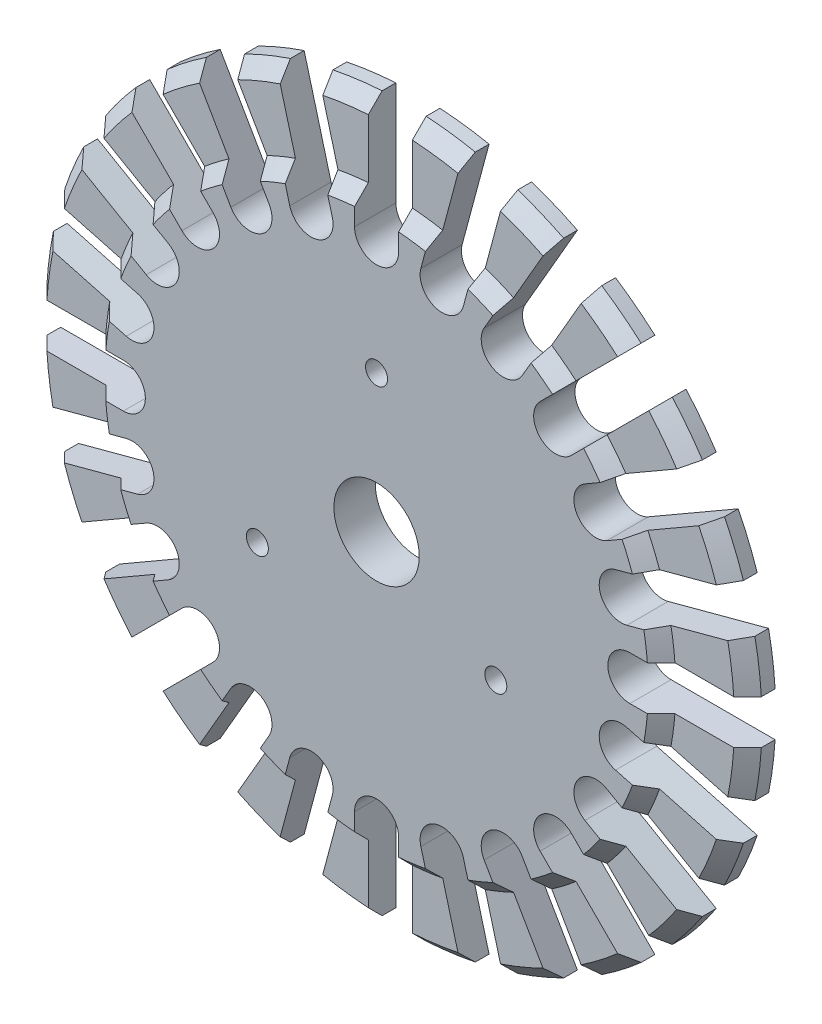
SolidWorks part; units mm, degrees
ref_plane "Plano frontal" through (0, 0, 0) normal (0, 0, 1) x (1, 0, 0)
ref_plane "Plano superior" through (0, 0, 0) normal (0, 1, 0) x (1, 0, 0)
ref_plane "Plano direito" through (0, 0, 0) normal (1, 0, 0) x (0, 0, -1)
sketch "Esboço1" plane through (0, 0, 0) normal (0, 0, 1) x (1, 0, 0)
  line L0 (0, 0) -> (26, 0) construction
  circle A0 centre (0, 0) radius 26
  dimension "R1" = 52
extrude "Ressalto-extrusão1" add sketch "Esboço1" along normal blind 2
fillet "Chanfro1" radius 1 1 edges at (26, 0, 2) type face fillet profile chamfer first side face at (26, 0, 2) second side face at (26, 0, 2)
sketch "Esboço3" plane through (0, 0, 0) normal (0, 0, -1) x (-1, 0, 0)
  line L0 (0, 0) -> (26, 0) construction
  line L1 (18.4, 1.6) -> (18.4, -1.6) construction
  line L2 (18.4, -1.6) -> (25.9507, -1.6)
  line L3 (18.4, 1.6) -> (25.9507, 1.6)
  line L4 (17.3589, -6.3078) -> (24.6524, -8.262)
  line L5 (18.1871, -3.2168) -> (25.4806, -5.1711)
  line L6 (0, 0) -> (25.1141, -6.7293) construction
  line L7 (15.1349, -10.5856) -> (21.674, -14.361)
  line L8 (16.7349, -7.8144) -> (23.274, -11.5897)
  line L9 (0, 0) -> (22.5167, -13) construction
  line L10 (11.8794, -14.1421) -> (17.2186, -19.4813)
  line L11 (14.1421, -11.8794) -> (19.4813, -17.2186)
  line L12 (0, 0) -> (18.3848, -18.3848) construction
  line L13 (7.8144, -16.7349) -> (11.5897, -23.274)
  line L14 (10.5856, -15.1349) -> (14.361, -21.674)
  line L15 (0, 0) -> (13, -22.5167) construction
  line L16 (3.2168, -18.1871) -> (5.1711, -25.4806)
  line L17 (6.3078, -17.3589) -> (8.262, -24.6524)
  line L18 (0, 0) -> (6.7293, -25.1141) construction
  line L19 (-1.6, -18.4) -> (-1.6, -25.9507)
  line L20 (1.6, -18.4) -> (1.6, -25.9507)
  line L21 (0, 0) -> (0, -26) construction
  line L22 (-6.3078, -17.3589) -> (-8.262, -24.6524)
  line L23 (-3.2168, -18.1871) -> (-5.1711, -25.4806)
  line L24 (0, 0) -> (-6.7293, -25.1141) construction
  line L25 (-10.5856, -15.1349) -> (-14.361, -21.674)
  line L26 (-7.8144, -16.7349) -> (-11.5897, -23.274)
  line L27 (0, 0) -> (-13, -22.5167) construction
  line L28 (-14.1421, -11.8794) -> (-19.4813, -17.2186)
  line L29 (-11.8794, -14.1421) -> (-17.2186, -19.4813)
  line L30 (0, 0) -> (-18.3848, -18.3848) construction
  line L31 (-16.7349, -7.8144) -> (-23.274, -11.5897)
  line L32 (-15.1349, -10.5856) -> (-21.674, -14.361)
  line L33 (0, 0) -> (-22.5167, -13) construction
  line L34 (-18.1871, -3.2168) -> (-25.4806, -5.1711)
  line L35 (-17.3589, -6.3078) -> (-24.6524, -8.262)
  line L36 (0, 0) -> (-25.1141, -6.7293) construction
  line L37 (-18.4, 1.6) -> (-25.9507, 1.6)
  line L38 (-18.4, -1.6) -> (-25.9507, -1.6)
  line L39 (0, 0) -> (-26, 0) construction
  line L40 (-17.3589, 6.3078) -> (-24.6524, 8.262)
  line L41 (-18.1871, 3.2168) -> (-25.4806, 5.1711)
  line L42 (0, 0) -> (-25.1141, 6.7293) construction
  line L43 (-15.1349, 10.5856) -> (-21.674, 14.361)
  line L44 (-16.7349, 7.8144) -> (-23.274, 11.5897)
  line L45 (0, 0) -> (-22.5167, 13) construction
  line L46 (-11.8794, 14.1421) -> (-17.2186, 19.4813)
  line L47 (-14.1421, 11.8794) -> (-19.4813, 17.2186)
  line L48 (0, 0) -> (-18.3848, 18.3848) construction
  line L49 (-7.8144, 16.7349) -> (-11.5897, 23.274)
  line L50 (-10.5856, 15.1349) -> (-14.361, 21.674)
  line L51 (0, 0) -> (-13, 22.5167) construction
  line L52 (-3.2168, 18.1871) -> (-5.1711, 25.4806)
  line L53 (-6.3078, 17.3589) -> (-8.262, 24.6524)
  line L54 (0, 0) -> (-6.7293, 25.1141) construction
  line L55 (1.6, 18.4) -> (1.6, 25.9507)
  line L56 (-1.6, 18.4) -> (-1.6, 25.9507)
  line L57 (0, 0) -> (0, 26) construction
  line L58 (6.3078, 17.3589) -> (8.262, 24.6524)
  line L59 (3.2168, 18.1871) -> (5.1711, 25.4806)
  line L60 (0, 0) -> (6.7293, 25.1141) construction
  line L61 (10.5856, 15.1349) -> (14.361, 21.674)
  line L62 (7.8144, 16.7349) -> (11.5897, 23.274)
  line L63 (0, 0) -> (13, 22.5167) construction
  line L64 (14.1421, 11.8794) -> (19.4813, 17.2186)
  line L65 (11.8794, 14.1421) -> (17.2186, 19.4813)
  line L66 (0, 0) -> (18.3848, 18.3848) construction
  line L67 (16.7349, 7.8144) -> (23.274, 11.5897)
  line L68 (15.1349, 10.5856) -> (21.674, 14.361)
  line L69 (0, 0) -> (22.5167, 13) construction
  line L70 (18.1871, 3.2168) -> (25.4806, 5.1711)
  line L71 (17.3589, 6.3078) -> (24.6524, 8.262)
  line L72 (0, 0) -> (25.1141, 6.7293) construction
  arc A1 (18.4, -1.6) -> (18.4, 1.6) centre (18.4, 0) cw
  arc A2 (25.9507, 1.6) -> (25.9507, -1.6) centre (0, 0) cw
  arc A3 (17.3589, -6.3078) -> (18.1871, -3.2168) centre (17.773, -4.7623) cw
  arc A4 (25.4806, -5.1711) -> (24.6524, -8.262) centre (0, 0) cw
  arc A5 (15.1349, -10.5856) -> (16.7349, -7.8144) centre (15.9349, -9.2) cw
  arc A6 (23.274, -11.5897) -> (21.674, -14.361) centre (0, 0) cw
  arc A7 (11.8794, -14.1421) -> (14.1421, -11.8794) centre (13.0108, -13.0108) cw
  arc A8 (19.4813, -17.2186) -> (17.2186, -19.4813) centre (0, 0) cw
  arc A9 (7.8144, -16.7349) -> (10.5856, -15.1349) centre (9.2, -15.9349) cw
  arc A10 (14.361, -21.674) -> (11.5897, -23.274) centre (0, 0) cw
  arc A11 (3.2168, -18.1871) -> (6.3078, -17.3589) centre (4.7623, -17.773) cw
  arc A12 (8.262, -24.6524) -> (5.1711, -25.4806) centre (0, 0) cw
  arc A13 (-1.6, -18.4) -> (1.6, -18.4) centre (0, -18.4) cw
  arc A14 (1.6, -25.9507) -> (-1.6, -25.9507) centre (0, 0) cw
  arc A15 (-6.3078, -17.3589) -> (-3.2168, -18.1871) centre (-4.7623, -17.773) cw
  arc A16 (-5.1711, -25.4806) -> (-8.262, -24.6524) centre (0, 0) cw
  arc A17 (-10.5856, -15.1349) -> (-7.8144, -16.7349) centre (-9.2, -15.9349) cw
  arc A18 (-11.5897, -23.274) -> (-14.361, -21.674) centre (0, 0) cw
  arc A19 (-14.1421, -11.8794) -> (-11.8794, -14.1421) centre (-13.0108, -13.0108) cw
  arc A20 (-17.2186, -19.4813) -> (-19.4813, -17.2186) centre (0, 0) cw
  arc A21 (-16.7349, -7.8144) -> (-15.1349, -10.5856) centre (-15.9349, -9.2) cw
  arc A22 (-21.674, -14.361) -> (-23.274, -11.5897) centre (0, 0) cw
  arc A23 (-18.1871, -3.2168) -> (-17.3589, -6.3078) centre (-17.773, -4.7623) cw
  arc A24 (-24.6524, -8.262) -> (-25.4806, -5.1711) centre (0, 0) cw
  arc A25 (-18.4, 1.6) -> (-18.4, -1.6) centre (-18.4, 0) cw
  arc A26 (-25.9507, -1.6) -> (-25.9507, 1.6) centre (0, 0) cw
  arc A27 (-17.3589, 6.3078) -> (-18.1871, 3.2168) centre (-17.773, 4.7623) cw
  arc A28 (-25.4806, 5.1711) -> (-24.6524, 8.262) centre (0, 0) cw
  arc A29 (-15.1349, 10.5856) -> (-16.7349, 7.8144) centre (-15.9349, 9.2) cw
  arc A30 (-23.274, 11.5897) -> (-21.674, 14.361) centre (0, 0) cw
  arc A31 (-11.8794, 14.1421) -> (-14.1421, 11.8794) centre (-13.0108, 13.0108) cw
  arc A32 (-19.4813, 17.2186) -> (-17.2186, 19.4813) centre (0, 0) cw
  arc A33 (-7.8144, 16.7349) -> (-10.5856, 15.1349) centre (-9.2, 15.9349) cw
  arc A34 (-14.361, 21.674) -> (-11.5897, 23.274) centre (0, 0) cw
  arc A35 (-3.2168, 18.1871) -> (-6.3078, 17.3589) centre (-4.7623, 17.773) cw
  arc A36 (-8.262, 24.6524) -> (-5.1711, 25.4806) centre (0, 0) cw
  arc A37 (1.6, 18.4) -> (-1.6, 18.4) centre (0, 18.4) cw
  arc A38 (-1.6, 25.9507) -> (1.6, 25.9507) centre (0, 0) cw
  arc A39 (6.3078, 17.3589) -> (3.2168, 18.1871) centre (4.7623, 17.773) cw
  arc A40 (5.1711, 25.4806) -> (8.262, 24.6524) centre (0, 0) cw
  arc A41 (10.5856, 15.1349) -> (7.8144, 16.7349) centre (9.2, 15.9349) cw
  arc A42 (11.5897, 23.274) -> (14.361, 21.674) centre (0, 0) cw
  arc A43 (14.1421, 11.8794) -> (11.8794, 14.1421) centre (13.0108, 13.0108) cw
  arc A44 (17.2186, 19.4813) -> (19.4813, 17.2186) centre (0, 0) cw
  arc A45 (16.7349, 7.8144) -> (15.1349, 10.5856) centre (15.9349, 9.2) cw
  arc A46 (21.674, 14.361) -> (23.274, 11.5897) centre (0, 0) cw
  arc A47 (18.1871, 3.2168) -> (17.3589, 6.3078) centre (17.773, 4.7623) cw
  arc A48 (24.6524, 8.262) -> (25.4806, 5.1711) centre (0, 0) cw
  circle A51 centre (0, 0) radius 26
  circle A53 centre (0, 0) radius 26
  point P9 (18.4, 0)
  point P20 (17.773, -4.7623)
  point P27 (15.9349, -9.2)
  point P34 (13.0108, -13.0108)
  point P41 (9.2, -15.9349)
  point P48 (4.7623, -17.773)
  point P55 (0, -18.4)
  point P62 (-4.7623, -17.773)
  point P69 (-9.2, -15.9349)
  point P76 (-13.0108, -13.0108)
  point P83 (-15.9349, -9.2)
  point P90 (-17.773, -4.7623)
  point P97 (-18.4, 0)
  point P104 (-17.773, 4.7623)
  point P111 (-15.9349, 9.2)
  point P118 (-13.0108, 13.0108)
  point P125 (-9.2, 15.9349)
  point P132 (-4.7623, 17.773)
  point P139 (0, 18.4)
  point P146 (4.7623, 17.773)
  point P153 (9.2, 15.9349)
  point P160 (13.0108, 13.0108)
  point P167 (15.9349, 9.2)
  point P174 (17.773, 4.7623)
  point P177 (0, 0)
  circle M5 centre (0, 0) radius 26
  dimension "D1" = 3.2
  dimension "D2" = 7.6
  dimension "D4" = 0
  dimension "D3" = 24
extrude "Corte-extrusão1" cut sketch "Esboço3" against normal through all contours A1 L2 L3 M5 | A3 L4 L5 M5 | A5 L7 L8 M5 | A7 L10 L11 M5 | A9 L13 L14 M5 | A11 L16 L17 M5 | A13 L19 L20 M5 | A15 L22 L23 M5 | A17 L25 L26 M5 | A19 L28 L29 M5 | A21 L31 L32 M5 | A23 L34 L35 M5 | A25 L37 L38 M5 | A29 L43 L44 M5 | A27 L40 L41 M5 | A31 L46 L47 M5 | A33 L49 L50 M5 | A37 L55 L56 M5 | A39 L58 L59 M5 | A41 L61 L62 M5 | A43 L64 L65 M5 | A47 L70 L71 M5 | A45 L67 L68 M5 | L52 A36 L53 A35 region at (-21.5563, 0, 0) region at (-20.8218, -5.5792, 0) region at (-20.8218, 5.5792, 0) region at (-18.6683, -10.7781, 0) region at (-18.6683, 10.7781, 0) region at (-15.2426, -15.2426, 0) region at (-15.2426, 15.2426, 0) region at (-10.7781, -18.6683, 0) region at (-10.7781, 18.6683, 0) region at (-5.5792, -20.8218, 0) region at (-5.5792, 20.8218, 0) region at (0, -21.5563, 0) region at (0, 21.5563, 0) region at (5.5792, -20.8218, 0) region at (10.7781, -18.6683, 0) region at (10.7781, 18.6683, 0) region at (15.2426, -15.2426, 0) region at (15.2426, 15.2426, 0) region at (18.6683, -10.7781, 0) region at (18.6683, 10.7781, 0) region at (20.8218, -5.5792, 0) region at (20.8218, 5.5792, 0) region at (21.5563, 0, 0)
sketch "Esboço4" plane through (0, 0, 0) normal (0, 0, -1) x (-1, 0, 0)
  line L0 (22.9466, 1.6) -> (22.9466, 2.6)
  line L1 (0, 0) -> (20.78, -7.2244) construction
  line L2 (25.9507, 1.6) -> (18.4, 1.6) construction
  line L3 (0, 0) -> (21.6082, -4.1335) construction
  line L4 (18.4, -1.6) -> (25.9507, -1.6) construction
  line L5 (0, 0) -> (0, 6.1074) construction
  line L6 (0, 0) -> (23.9466, 1.6) construction
  line L7 (0, 0) -> (23.9466, -1.6) construction
  line L8 (0, 0) -> (18.2021, -12.3565) construction
  line L9 (0, 0) -> (19.8021, -9.5852) construction
  line L10 (0, 0) -> (14.3838, -16.6465) construction
  line L11 (0, 0) -> (16.6465, -14.3838) construction
  line L12 (0, 0) -> (9.5852, -19.8021) construction
  line L13 (0, 0) -> (12.3565, -18.2021) construction
  line L14 (0, 0) -> (4.1335, -21.6082) construction
  line L15 (0, 0) -> (7.2244, -20.78) construction
  line L16 (0, 0) -> (-1.6, -21.9417) construction
  line L17 (0, 0) -> (1.6, -21.9417) construction
  line L18 (0, 0) -> (-7.2244, -20.78) construction
  line L19 (0, 0) -> (-4.1335, -21.6082) construction
  line L20 (0, 0) -> (-12.3565, -18.2021) construction
  line L21 (0, 0) -> (-9.5852, -19.8021) construction
  line L22 (0, 0) -> (-16.6465, -14.3838) construction
  line L23 (0, 0) -> (-14.3838, -16.6465) construction
  line L24 (0, 0) -> (-19.8021, -9.5852) construction
  line L25 (0, 0) -> (-18.2021, -12.3565) construction
  line L26 (0, 0) -> (-21.6082, -4.1335) construction
  line L27 (0, 0) -> (-20.78, -7.2244) construction
  line L28 (0, 0) -> (-21.9417, 1.6) construction
  line L29 (0, 0) -> (-21.9417, -1.6) construction
  line L30 (0, 0) -> (-20.78, 7.2244) construction
  line L31 (0, 0) -> (-21.6082, 4.1335) construction
  line L32 (0, 0) -> (-18.2021, 12.3565) construction
  line L33 (0, 0) -> (-19.8021, 9.5852) construction
  line L34 (0, 0) -> (-14.3838, 16.6465) construction
  line L35 (0, 0) -> (-16.6465, 14.3838) construction
  line L36 (0, 0) -> (-9.5852, 19.8021) construction
  line L37 (0, 0) -> (-12.3565, 18.2021) construction
  line L38 (0, 0) -> (-4.1335, 21.6082) construction
  line L39 (0, 0) -> (-7.2244, 20.78) construction
  line L40 (0, 0) -> (1.6, 21.9417) construction
  line L41 (0, 0) -> (-1.6, 21.9417) construction
  line L42 (0, 0) -> (7.2244, 20.78) construction
  line L43 (0, 0) -> (4.1335, 21.6082) construction
  line L44 (0, 0) -> (12.3565, 18.2021) construction
  line L45 (0, 0) -> (9.5852, 19.8021) construction
  line L52 (22.9466, 2.6) -> (24.9466, 2.6)
  line L54 (0, 0) -> (0, 10) construction
  line L55 (24.9466, -2.6) -> (22.9466, -2.6)
  line L57 (23.9466, 1.6) -> (23.9466, -1.6) construction
  line L58 (22.9466, -1.6) -> (22.9466, -2.6)
  line L59 (22.9466, 2.6) -> (22.9466, -2.6) construction
  line L60 (24.9466, -2.6) -> (24.9466, 2.6) construction
  line L61 (24.9466, -2.6) -> (24.9466, -1.6)
  line L62 (24.9466, -1.6) -> (22.9466, -1.6)
  line L63 (24.9466, 1.6) -> (22.9466, 1.6)
  line L64 (24.9466, 1.6) -> (24.9466, 2.6)
  line L65 (22.5788, -4.3935) -> (22.8377, -3.4276)
  line L66 (22.8377, -3.4276) -> (24.7695, -3.9452)
  line L67 (23.4236, -8.9681) -> (21.4918, -8.4504)
  line L68 (21.7506, -7.4845) -> (21.4918, -8.4504)
  line L69 (23.4236, -8.9681) -> (23.6825, -8.0021)
  line L70 (23.6825, -8.0021) -> (21.7506, -7.4845)
  line L71 (24.5107, -4.9112) -> (22.5788, -4.3935)
  line L72 (24.5107, -4.9112) -> (24.7695, -3.9452)
  line L73 (0, 0) -> (23.5448, -4.6524) construction
  line L74 (0, 0) -> (22.7165, -7.7433) construction
  line L75 (22.8377, -3.4276) -> (21.4918, -8.4504) construction
  line L76 (23.4236, -8.9681) -> (24.7695, -3.9452) construction
  line L77 (20.6723, -10.0877) -> (21.1723, -9.2216)
  line L78 (21.1723, -9.2216) -> (22.9044, -10.2216)
  line L79 (20.3044, -14.725) -> (18.5723, -13.725)
  line L80 (19.0723, -12.8589) -> (18.5723, -13.725)
  line L81 (20.3044, -14.725) -> (20.8044, -13.8589)
  line L82 (20.8044, -13.8589) -> (19.0723, -12.8589)
  line L83 (22.4044, -11.0877) -> (20.6723, -10.0877)
  line L84 (22.4044, -11.0877) -> (22.9044, -10.2216)
  line L85 (0, 0) -> (21.5384, -10.5877) construction
  line L86 (0, 0) -> (19.9384, -13.3589) construction
  line L87 (21.1723, -9.2216) -> (18.5723, -13.725) construction
  line L88 (20.3044, -14.725) -> (22.9044, -10.2216) construction
  line L89 (17.3571, -15.0943) -> (18.0642, -14.3872)
  line L90 (18.0642, -14.3872) -> (19.4784, -15.8014)
  line L91 (15.8014, -19.4784) -> (14.3872, -18.0642)
  line L92 (15.0943, -17.3571) -> (14.3872, -18.0642)
  line L93 (15.8014, -19.4784) -> (16.5085, -18.7713)
  line L94 (16.5085, -18.7713) -> (15.0943, -17.3571)
  line L95 (18.7713, -16.5085) -> (17.3571, -15.0943)
  line L96 (18.7713, -16.5085) -> (19.4784, -15.8014)
  line L97 (0, 0) -> (18.0642, -15.8014) construction
  line L98 (0, 0) -> (15.8014, -18.0642) construction
  line L99 (18.0642, -14.3872) -> (14.3872, -18.0642) construction
  line L100 (15.8014, -19.4784) -> (19.4784, -15.8014) construction
  line L101 (12.8589, -19.0723) -> (13.725, -18.5723)
  line L102 (13.725, -18.5723) -> (14.725, -20.3044)
  line L103 (10.2216, -22.9044) -> (9.2216, -21.1723)
  line L104 (10.0877, -20.6723) -> (9.2216, -21.1723)
  line L105 (10.2216, -22.9044) -> (11.0877, -22.4044)
  line L106 (11.0877, -22.4044) -> (10.0877, -20.6723)
  line L107 (13.8589, -20.8044) -> (12.8589, -19.0723)
  line L108 (13.8589, -20.8044) -> (14.725, -20.3044)
  line L109 (0, 0) -> (13.3589, -19.9384) construction
  line L110 (0, 0) -> (10.5877, -21.5384) construction
  line L111 (13.725, -18.5723) -> (9.2216, -21.1723) construction
  line L112 (10.2216, -22.9044) -> (14.725, -20.3044) construction
  line L113 (7.4845, -21.7506) -> (8.4504, -21.4918)
  line L114 (8.4504, -21.4918) -> (8.9681, -23.4236)
  line L115 (3.9452, -24.7695) -> (3.4276, -22.8377)
  line L116 (4.3935, -22.5788) -> (3.4276, -22.8377)
  line L117 (3.9452, -24.7695) -> (4.9112, -24.5107)
  line L118 (4.9112, -24.5107) -> (4.3935, -22.5788)
  line L119 (8.0021, -23.6825) -> (7.4845, -21.7506)
  line L120 (8.0021, -23.6825) -> (8.9681, -23.4236)
  line L121 (0, 0) -> (7.7433, -22.7165) construction
  line L122 (0, 0) -> (4.6524, -23.5448) construction
  line L123 (8.4504, -21.4918) -> (3.4276, -22.8377) construction
  line L124 (3.9452, -24.7695) -> (8.9681, -23.4236) construction
  line L125 (1.6, -22.9466) -> (2.6, -22.9466)
  line L126 (2.6, -22.9466) -> (2.6, -24.9466)
  line L127 (-2.6, -24.9466) -> (-2.6, -22.9466)
  line L128 (-1.6, -22.9466) -> (-2.6, -22.9466)
  line L129 (-2.6, -24.9466) -> (-1.6, -24.9466)
  line L130 (-1.6, -24.9466) -> (-1.6, -22.9466)
  line L131 (1.6, -24.9466) -> (1.6, -22.9466)
  line L132 (1.6, -24.9466) -> (2.6, -24.9466)
  line L133 (0, 0) -> (1.6, -23.9466) construction
  line L134 (0, 0) -> (-1.6, -23.9466) construction
  line L135 (2.6, -22.9466) -> (-2.6, -22.9466) construction
  line L136 (-2.6, -24.9466) -> (2.6, -24.9466) construction
  line L137 (-4.3935, -22.5788) -> (-3.4276, -22.8377)
  line L138 (-3.4276, -22.8377) -> (-3.9452, -24.7695)
  line L139 (-8.9681, -23.4236) -> (-8.4504, -21.4918)
  line L140 (-7.4845, -21.7506) -> (-8.4504, -21.4918)
  line L141 (-8.9681, -23.4236) -> (-8.0021, -23.6825)
  line L142 (-8.0021, -23.6825) -> (-7.4845, -21.7506)
  line L143 (-4.9112, -24.5107) -> (-4.3935, -22.5788)
  line L144 (-4.9112, -24.5107) -> (-3.9452, -24.7695)
  line L145 (0, 0) -> (-4.6524, -23.5448) construction
  line L146 (0, 0) -> (-7.7433, -22.7165) construction
  line L147 (-3.4276, -22.8377) -> (-8.4504, -21.4918) construction
  line L148 (-8.9681, -23.4236) -> (-3.9452, -24.7695) construction
  line L149 (-10.0877, -20.6723) -> (-9.2216, -21.1723)
  line L150 (-9.2216, -21.1723) -> (-10.2216, -22.9044)
  line L151 (-14.725, -20.3044) -> (-13.725, -18.5723)
  line L152 (-12.8589, -19.0723) -> (-13.725, -18.5723)
  line L153 (-14.725, -20.3044) -> (-13.8589, -20.8044)
  line L154 (-13.8589, -20.8044) -> (-12.8589, -19.0723)
  line L155 (-11.0877, -22.4044) -> (-10.0877, -20.6723)
  line L156 (-11.0877, -22.4044) -> (-10.2216, -22.9044)
  line L157 (0, 0) -> (-10.5877, -21.5384) construction
  line L158 (0, 0) -> (-13.3589, -19.9384) construction
  line L159 (-9.2216, -21.1723) -> (-13.725, -18.5723) construction
  line L160 (-14.725, -20.3044) -> (-10.2216, -22.9044) construction
  line L161 (-15.0943, -17.3571) -> (-14.3872, -18.0642)
  line L162 (-14.3872, -18.0642) -> (-15.8014, -19.4784)
  line L163 (-19.4784, -15.8014) -> (-18.0642, -14.3872)
  line L164 (-17.3571, -15.0943) -> (-18.0642, -14.3872)
  line L165 (-19.4784, -15.8014) -> (-18.7713, -16.5085)
  line L166 (-18.7713, -16.5085) -> (-17.3571, -15.0943)
  line L167 (-16.5085, -18.7713) -> (-15.0943, -17.3571)
  line L168 (-16.5085, -18.7713) -> (-15.8014, -19.4784)
  line L169 (0, 0) -> (-15.8014, -18.0642) construction
  line L170 (0, 0) -> (-18.0642, -15.8014) construction
  line L171 (-14.3872, -18.0642) -> (-18.0642, -14.3872) construction
  line L172 (-19.4784, -15.8014) -> (-15.8014, -19.4784) construction
  line L173 (-19.0723, -12.8589) -> (-18.5723, -13.725)
  line L174 (-18.5723, -13.725) -> (-20.3044, -14.725)
  line L175 (-22.9044, -10.2216) -> (-21.1723, -9.2216)
  line L176 (-20.6723, -10.0877) -> (-21.1723, -9.2216)
  line L177 (-22.9044, -10.2216) -> (-22.4044, -11.0877)
  line L178 (-22.4044, -11.0877) -> (-20.6723, -10.0877)
  line L179 (-20.8044, -13.8589) -> (-19.0723, -12.8589)
  line L180 (-20.8044, -13.8589) -> (-20.3044, -14.725)
  line L181 (0, 0) -> (-19.9384, -13.3589) construction
  line L182 (0, 0) -> (-21.5384, -10.5877) construction
  line L183 (-18.5723, -13.725) -> (-21.1723, -9.2216) construction
  line L184 (-22.9044, -10.2216) -> (-20.3044, -14.725) construction
  line L185 (-21.7506, -7.4845) -> (-21.4918, -8.4504)
  line L186 (-21.4918, -8.4504) -> (-23.4236, -8.9681)
  line L187 (-24.7695, -3.9452) -> (-22.8377, -3.4276)
  line L188 (-22.5788, -4.3935) -> (-22.8377, -3.4276)
  line L189 (-24.7695, -3.9452) -> (-24.5107, -4.9112)
  line L190 (-24.5107, -4.9112) -> (-22.5788, -4.3935)
  line L191 (-23.6825, -8.0021) -> (-21.7506, -7.4845)
  line L192 (-23.6825, -8.0021) -> (-23.4236, -8.9681)
  line L193 (0, 0) -> (-22.7165, -7.7433) construction
  line L194 (0, 0) -> (-23.5448, -4.6524) construction
  line L195 (-21.4918, -8.4504) -> (-22.8377, -3.4276) construction
  line L196 (-24.7695, -3.9452) -> (-23.4236, -8.9681) construction
  line L197 (-22.9466, -1.6) -> (-22.9466, -2.6)
  line L198 (-22.9466, -2.6) -> (-24.9466, -2.6)
  line L199 (-24.9466, 2.6) -> (-22.9466, 2.6)
  line L200 (-22.9466, 1.6) -> (-22.9466, 2.6)
  line L201 (-24.9466, 2.6) -> (-24.9466, 1.6)
  line L202 (-24.9466, 1.6) -> (-22.9466, 1.6)
  line L203 (-24.9466, -1.6) -> (-22.9466, -1.6)
  line L204 (-24.9466, -1.6) -> (-24.9466, -2.6)
  line L205 (0, 0) -> (-23.9466, -1.6) construction
  line L206 (0, 0) -> (-23.9466, 1.6) construction
  line L207 (-22.9466, -2.6) -> (-22.9466, 2.6) construction
  line L208 (-24.9466, 2.6) -> (-24.9466, -2.6) construction
  line L209 (-22.5788, 4.3935) -> (-22.8377, 3.4276)
  line L210 (-22.8377, 3.4276) -> (-24.7695, 3.9452)
  line L211 (-23.4236, 8.9681) -> (-21.4918, 8.4504)
  line L212 (-21.7506, 7.4845) -> (-21.4918, 8.4504)
  line L213 (-23.4236, 8.9681) -> (-23.6825, 8.0021)
  line L214 (-23.6825, 8.0021) -> (-21.7506, 7.4845)
  line L215 (-24.5107, 4.9112) -> (-22.5788, 4.3935)
  line L216 (-24.5107, 4.9112) -> (-24.7695, 3.9452)
  line L217 (0, 0) -> (-23.5448, 4.6524) construction
  line L218 (0, 0) -> (-22.7165, 7.7433) construction
  line L219 (-22.8377, 3.4276) -> (-21.4918, 8.4504) construction
  line L220 (-23.4236, 8.9681) -> (-24.7695, 3.9452) construction
  line L221 (-20.6723, 10.0877) -> (-21.1723, 9.2216)
  line L222 (-21.1723, 9.2216) -> (-22.9044, 10.2216)
  line L223 (-20.3044, 14.725) -> (-18.5723, 13.725)
  line L224 (-19.0723, 12.8589) -> (-18.5723, 13.725)
  line L225 (-20.3044, 14.725) -> (-20.8044, 13.8589)
  line L226 (-20.8044, 13.8589) -> (-19.0723, 12.8589)
  line L227 (-22.4044, 11.0877) -> (-20.6723, 10.0877)
  line L228 (-22.4044, 11.0877) -> (-22.9044, 10.2216)
  line L229 (0, 0) -> (-21.5384, 10.5877) construction
  line L230 (0, 0) -> (-19.9384, 13.3589) construction
  line L231 (-21.1723, 9.2216) -> (-18.5723, 13.725) construction
  line L232 (-20.3044, 14.725) -> (-22.9044, 10.2216) construction
  line L233 (-17.3571, 15.0943) -> (-18.0642, 14.3872)
  line L234 (-18.0642, 14.3872) -> (-19.4784, 15.8014)
  line L235 (-15.8014, 19.4784) -> (-14.3872, 18.0642)
  line L236 (-15.0943, 17.3571) -> (-14.3872, 18.0642)
  line L237 (-15.8014, 19.4784) -> (-16.5085, 18.7713)
  line L238 (-16.5085, 18.7713) -> (-15.0943, 17.3571)
  line L239 (-18.7713, 16.5085) -> (-17.3571, 15.0943)
  line L240 (-18.7713, 16.5085) -> (-19.4784, 15.8014)
  line L241 (0, 0) -> (-18.0642, 15.8014) construction
  line L242 (0, 0) -> (-15.8014, 18.0642) construction
  line L243 (-18.0642, 14.3872) -> (-14.3872, 18.0642) construction
  line L244 (-15.8014, 19.4784) -> (-19.4784, 15.8014) construction
  line L245 (-12.8589, 19.0723) -> (-13.725, 18.5723)
  line L246 (-13.725, 18.5723) -> (-14.725, 20.3044)
  line L247 (-10.2216, 22.9044) -> (-9.2216, 21.1723)
  line L248 (-10.0877, 20.6723) -> (-9.2216, 21.1723)
  line L249 (-10.2216, 22.9044) -> (-11.0877, 22.4044)
  line L250 (-11.0877, 22.4044) -> (-10.0877, 20.6723)
  line L251 (-13.8589, 20.8044) -> (-12.8589, 19.0723)
  line L252 (-13.8589, 20.8044) -> (-14.725, 20.3044)
  line L253 (0, 0) -> (-13.3589, 19.9384) construction
  line L254 (0, 0) -> (-10.5877, 21.5384) construction
  line L255 (-13.725, 18.5723) -> (-9.2216, 21.1723) construction
  line L256 (-10.2216, 22.9044) -> (-14.725, 20.3044) construction
  line L257 (-7.4845, 21.7506) -> (-8.4504, 21.4918)
  line L258 (-8.4504, 21.4918) -> (-8.9681, 23.4236)
  line L259 (-3.9452, 24.7695) -> (-3.4276, 22.8377)
  line L260 (-4.3935, 22.5788) -> (-3.4276, 22.8377)
  line L261 (-3.9452, 24.7695) -> (-4.9112, 24.5107)
  line L262 (-4.9112, 24.5107) -> (-4.3935, 22.5788)
  line L263 (-8.0021, 23.6825) -> (-7.4845, 21.7506)
  line L264 (-8.0021, 23.6825) -> (-8.9681, 23.4236)
  line L265 (0, 0) -> (-7.7433, 22.7165) construction
  line L266 (0, 0) -> (-4.6524, 23.5448) construction
  line L267 (-8.4504, 21.4918) -> (-3.4276, 22.8377) construction
  line L268 (-3.9452, 24.7695) -> (-8.9681, 23.4236) construction
  line L269 (-1.6, 22.9466) -> (-2.6, 22.9466)
  line L270 (-2.6, 22.9466) -> (-2.6, 24.9466)
  line L271 (2.6, 24.9466) -> (2.6, 22.9466)
  line L272 (1.6, 22.9466) -> (2.6, 22.9466)
  line L273 (2.6, 24.9466) -> (1.6, 24.9466)
  line L274 (1.6, 24.9466) -> (1.6, 22.9466)
  line L275 (-1.6, 24.9466) -> (-1.6, 22.9466)
  line L276 (-1.6, 24.9466) -> (-2.6, 24.9466)
  line L277 (0, 0) -> (-1.6, 23.9466) construction
  line L278 (0, 0) -> (1.6, 23.9466) construction
  line L279 (-2.6, 22.9466) -> (2.6, 22.9466) construction
  line L280 (2.6, 24.9466) -> (-2.6, 24.9466) construction
  line L281 (4.3935, 22.5788) -> (3.4276, 22.8377)
  line L282 (3.4276, 22.8377) -> (3.9452, 24.7695)
  line L283 (8.9681, 23.4236) -> (8.4504, 21.4918)
  line L284 (7.4845, 21.7506) -> (8.4504, 21.4918)
  line L285 (8.9681, 23.4236) -> (8.0021, 23.6825)
  line L286 (8.0021, 23.6825) -> (7.4845, 21.7506)
  line L287 (4.9112, 24.5107) -> (4.3935, 22.5788)
  line L288 (4.9112, 24.5107) -> (3.9452, 24.7695)
  line L289 (0, 0) -> (4.6524, 23.5448) construction
  line L290 (0, 0) -> (7.7433, 22.7165) construction
  line L291 (3.4276, 22.8377) -> (8.4504, 21.4918) construction
  line L292 (8.9681, 23.4236) -> (3.9452, 24.7695) construction
  line L293 (10.0877, 20.6723) -> (9.2216, 21.1723)
  line L294 (9.2216, 21.1723) -> (10.2216, 22.9044)
  line L295 (14.725, 20.3044) -> (13.725, 18.5723)
  line L296 (12.8589, 19.0723) -> (13.725, 18.5723)
  line L297 (14.725, 20.3044) -> (13.8589, 20.8044)
  line L298 (13.8589, 20.8044) -> (12.8589, 19.0723)
  line L299 (11.0877, 22.4044) -> (10.0877, 20.6723)
  line L300 (11.0877, 22.4044) -> (10.2216, 22.9044)
  line L301 (0, 0) -> (10.5877, 21.5384) construction
  line L302 (0, 0) -> (13.3589, 19.9384) construction
  line L303 (9.2216, 21.1723) -> (13.725, 18.5723) construction
  line L304 (14.725, 20.3044) -> (10.2216, 22.9044) construction
  line L305 (15.0943, 17.3571) -> (14.3872, 18.0642)
  line L306 (14.3872, 18.0642) -> (15.8014, 19.4784)
  line L307 (19.4784, 15.8014) -> (18.0642, 14.3872)
  line L308 (17.3571, 15.0943) -> (18.0642, 14.3872)
  line L309 (19.4784, 15.8014) -> (18.7713, 16.5085)
  line L310 (18.7713, 16.5085) -> (17.3571, 15.0943)
  line L311 (16.5085, 18.7713) -> (15.0943, 17.3571)
  line L312 (16.5085, 18.7713) -> (15.8014, 19.4784)
  line L313 (0, 0) -> (15.8014, 18.0642) construction
  line L314 (0, 0) -> (18.0642, 15.8014) construction
  line L315 (14.3872, 18.0642) -> (18.0642, 14.3872) construction
  line L316 (19.4784, 15.8014) -> (15.8014, 19.4784) construction
  line L317 (19.0723, 12.8589) -> (18.5723, 13.725)
  line L318 (18.5723, 13.725) -> (20.3044, 14.725)
  line L319 (22.9044, 10.2216) -> (21.1723, 9.2216)
  line L320 (20.6723, 10.0877) -> (21.1723, 9.2216)
  line L321 (22.9044, 10.2216) -> (22.4044, 11.0877)
  line L322 (22.4044, 11.0877) -> (20.6723, 10.0877)
  line L323 (20.8044, 13.8589) -> (19.0723, 12.8589)
  line L324 (20.8044, 13.8589) -> (20.3044, 14.725)
  line L325 (0, 0) -> (19.9384, 13.3589) construction
  line L326 (0, 0) -> (21.5384, 10.5877) construction
  line L327 (18.5723, 13.725) -> (21.1723, 9.2216) construction
  line L328 (22.9044, 10.2216) -> (20.3044, 14.725) construction
  line L329 (21.7506, 7.4845) -> (21.4918, 8.4504)
  line L330 (21.4918, 8.4504) -> (23.4236, 8.9681)
  line L331 (24.7695, 3.9452) -> (22.8377, 3.4276)
  line L332 (22.5788, 4.3935) -> (22.8377, 3.4276)
  line L333 (24.7695, 3.9452) -> (24.5107, 4.9112)
  line L334 (24.5107, 4.9112) -> (22.5788, 4.3935)
  line L335 (23.6825, 8.0021) -> (21.7506, 7.4845)
  line L336 (23.6825, 8.0021) -> (23.4236, 8.9681)
  line L337 (0, 0) -> (22.7165, 7.7433) construction
  line L338 (0, 0) -> (23.5448, 4.6524) construction
  line L339 (21.4918, 8.4504) -> (22.8377, 3.4276) construction
  line L340 (24.7695, 3.9452) -> (23.4236, 8.9681) construction
  line L341 (0, 0) -> (8.6603, -5) construction
  line L342 (0, 0) -> (-8.6603, -5) construction
  point P5 (20.78, -7.2244)
  point P8 (23.9466, 1.6)
  point P11 (23.9466, -1.6)
  point P13 (22.9466, -1.6)
  point P20 (18.2021, -12.3565)
  point P23 (14.3838, -16.6465)
  point P26 (9.5852, -19.8021)
  point P29 (4.1335, -21.6082)
  point P32 (-1.6, -21.9417)
  point P35 (-7.2244, -20.78)
  point P38 (-12.3565, -18.2021)
  point P41 (-16.6465, -14.3838)
  point P44 (-19.8021, -9.5852)
  point P47 (-21.6082, -4.1335)
  point P50 (-21.9417, 1.6)
  point P53 (-20.78, 7.2244)
  point P56 (-18.2021, 12.3565)
  point P59 (-14.3838, 16.6465)
  point P62 (-9.5852, 19.8021)
  point P65 (-4.1335, 21.6082)
  point P68 (1.6, 21.9417)
  point P71 (7.2244, 20.78)
  point P74 (12.3565, 18.2021)
  point P86 (0, 0)
  point P90 (0, 0)
  point P93 (24.9466, -1.6)
  point P94 (24.9466, 1.6)
  point P95 (24.9466, 1.6)
  point P98 (23.9466, 2.6)
  point P108 (23.5448, -4.6524)
  point P109 (22.7165, -7.7433)
  point P110 (21.7506, -7.4845)
  point P115 (23.6825, -8.0021)
  point P116 (24.5107, -4.9112)
  point P117 (24.5107, -4.9112)
  point P124 (21.5384, -10.5877)
  point P125 (19.9384, -13.3589)
  point P126 (19.0723, -12.8589)
  point P131 (20.8044, -13.8589)
  point P132 (22.4044, -11.0877)
  point P133 (22.4044, -11.0877)
  point P140 (18.0642, -15.8014)
  point P141 (15.8014, -18.0642)
  point P142 (15.0943, -17.3571)
  point P147 (16.5085, -18.7713)
  point P148 (18.7713, -16.5085)
  point P149 (18.7713, -16.5085)
  point P156 (13.3589, -19.9384)
  point P157 (10.5877, -21.5384)
  point P158 (10.0877, -20.6723)
  point P163 (11.0877, -22.4044)
  point P164 (13.8589, -20.8044)
  point P165 (13.8589, -20.8044)
  point P172 (7.7433, -22.7165)
  point P173 (4.6524, -23.5448)
  point P174 (4.3935, -22.5788)
  point P179 (4.9112, -24.5107)
  point P180 (8.0021, -23.6825)
  point P181 (8.0021, -23.6825)
  point P188 (1.6, -23.9466)
  point P189 (-1.6, -23.9466)
  point P190 (-1.6, -22.9466)
  point P195 (-1.6, -24.9466)
  point P196 (1.6, -24.9466)
  point P197 (1.6, -24.9466)
  point P204 (-4.6524, -23.5448)
  point P205 (-7.7433, -22.7165)
  point P206 (-7.4845, -21.7506)
  point P211 (-8.0021, -23.6825)
  point P212 (-4.9112, -24.5107)
  point P213 (-4.9112, -24.5107)
  point P220 (-10.5877, -21.5384)
  point P221 (-13.3589, -19.9384)
  point P222 (-12.8589, -19.0723)
  point P227 (-13.8589, -20.8044)
  point P228 (-11.0877, -22.4044)
  point P229 (-11.0877, -22.4044)
  point P236 (-15.8014, -18.0642)
  point P237 (-18.0642, -15.8014)
  point P238 (-17.3571, -15.0943)
  point P243 (-18.7713, -16.5085)
  point P244 (-16.5085, -18.7713)
  point P245 (-16.5085, -18.7713)
  point P252 (-19.9384, -13.3589)
  point P253 (-21.5384, -10.5877)
  point P254 (-20.6723, -10.0877)
  point P259 (-22.4044, -11.0877)
  point P260 (-20.8044, -13.8589)
  point P261 (-20.8044, -13.8589)
  point P268 (-22.7165, -7.7433)
  point P269 (-23.5448, -4.6524)
  point P270 (-22.5788, -4.3935)
  point P275 (-24.5107, -4.9112)
  point P276 (-23.6825, -8.0021)
  point P277 (-23.6825, -8.0021)
  point P284 (-23.9466, -1.6)
  point P285 (-23.9466, 1.6)
  point P286 (-22.9466, 1.6)
  point P291 (-24.9466, 1.6)
  point P292 (-24.9466, -1.6)
  point P293 (-24.9466, -1.6)
  point P300 (-23.5448, 4.6524)
  point P301 (-22.7165, 7.7433)
  point P302 (-21.7506, 7.4845)
  point P307 (-23.6825, 8.0021)
  point P308 (-24.5107, 4.9112)
  point P309 (-24.5107, 4.9112)
  point P316 (-21.5384, 10.5877)
  point P317 (-19.9384, 13.3589)
  point P318 (-19.0723, 12.8589)
  point P323 (-20.8044, 13.8589)
  point P324 (-22.4044, 11.0877)
  point P325 (-22.4044, 11.0877)
  point P332 (-18.0642, 15.8014)
  point P333 (-15.8014, 18.0642)
  point P334 (-15.0943, 17.3571)
  point P339 (-16.5085, 18.7713)
  point P340 (-18.7713, 16.5085)
  point P341 (-18.7713, 16.5085)
  point P348 (-13.3589, 19.9384)
  point P349 (-10.5877, 21.5384)
  point P350 (-10.0877, 20.6723)
  point P355 (-11.0877, 22.4044)
  point P356 (-13.8589, 20.8044)
  point P357 (-13.8589, 20.8044)
  point P364 (-7.7433, 22.7165)
  point P365 (-4.6524, 23.5448)
  point P366 (-4.3935, 22.5788)
  point P371 (-4.9112, 24.5107)
  point P372 (-8.0021, 23.6825)
  point P373 (-8.0021, 23.6825)
  point P380 (-1.6, 23.9466)
  point P381 (1.6, 23.9466)
  point P382 (1.6, 22.9466)
  point P387 (1.6, 24.9466)
  point P388 (-1.6, 24.9466)
  point P389 (-1.6, 24.9466)
  point P396 (4.6524, 23.5448)
  point P397 (7.7433, 22.7165)
  point P398 (7.4845, 21.7506)
  point P403 (8.0021, 23.6825)
  point P404 (4.9112, 24.5107)
  point P405 (4.9112, 24.5107)
  point P412 (10.5877, 21.5384)
  point P413 (13.3589, 19.9384)
  point P414 (12.8589, 19.0723)
  point P419 (13.8589, 20.8044)
  point P420 (11.0877, 22.4044)
  point P421 (11.0877, 22.4044)
  point P428 (15.8014, 18.0642)
  point P429 (18.0642, 15.8014)
  point P430 (17.3571, 15.0943)
  point P435 (18.7713, 16.5085)
  point P436 (16.5085, 18.7713)
  point P437 (16.5085, 18.7713)
  point P444 (19.9384, 13.3589)
  point P445 (21.5384, 10.5877)
  point P446 (20.6723, 10.0877)
  point P451 (22.4044, 11.0877)
  point P452 (20.8044, 13.8589)
  point P453 (20.8044, 13.8589)
  point P460 (22.7165, 7.7433)
  point P461 (23.5448, 4.6524)
  point P462 (22.5788, 4.3935)
  point P467 (24.5107, 4.9112)
  point P468 (23.6825, 8.0021)
  point P469 (23.6825, 8.0021)
  point P473 (0, 0)
  point P475 (0, 0)
  dimension "D1" = 24
  dimension "D2" = 2
  dimension "D4" = 1
  dimension "D5" = 10
  dimension "D6" = 24
sketch "Esboço8" plane through (0, 0, 2) normal (0, 0, 1) x (1, 0, 0)
  line L0 (18.4, 1.6) -> (24.9487, 1.6) construction
  line L1 (0, 0) -> (0, 10) construction
  line L2 (0, 0) -> (8.6603, -5) construction
  line L3 (0, 0) -> (-8.6603, -5) construction
  circle A0 centre (0, 0) radius 20.7362
  point P3 (21.6744, 1.6)
  point P4 (20.6744, 1.6)
  dimension "D1" = 1
extrude "Ressalto-extrusão2" add sketch "Esboço8" along normal blind 1
fillet "Chanfro2" radius 1 1 edges at (20.7362, 0, 3) type face fillet profile chamfer first side face at (20.7362, 0, 3) second side face at (20.7362, 0, 3)
sketch "Esboço9" plane through (0, 0, 2) normal (0, 0, -1) x (-1, 0, 0)
  line L0 (-11.7228, -17.1045) -> (-8.9515, -18.7045) construction
  line L1 (-8.9515, -18.7045) -> (-7.8144, -16.7349) construction
  line L2 (-10.3372, -17.9045) -> (0, 0) construction
  line L3 (-14.619, -14.619) -> (0, 0) construction
  line L4 (-10.5856, -15.1349) -> (-11.7228, -17.1045)
  line L5 (-8.9515, -18.7045) -> (-7.8144, -16.7349)
  line L8 (-17.9045, -10.3372) -> (0, 0) construction
  line L9 (-19.9699, -5.3509) -> (0, 0) construction
  line L10 (-20.6744, 0) -> (0, 0) construction
  line L11 (-19.9699, 5.3509) -> (0, 0) construction
  line L12 (-17.9045, 10.3372) -> (0, 0) construction
  line L13 (-14.619, 14.619) -> (0, 0) construction
  line L14 (-10.3372, 17.9045) -> (0, 0) construction
  line L15 (-5.3509, 19.9699) -> (0, 0) construction
  line L16 (0, 20.6744) -> (0, 0) construction
  line L17 (5.3509, 19.9699) -> (0, 0) construction
  line L18 (10.3372, 17.9045) -> (0, 0) construction
  line L19 (14.619, 14.619) -> (0, 0) construction
  line L20 (17.9045, 10.3372) -> (0, 0) construction
  line L21 (19.9699, 5.3509) -> (0, 0) construction
  line L22 (20.6744, 0) -> (0, 0) construction
  line L23 (19.9699, -5.3509) -> (0, 0) construction
  line L24 (17.9045, -10.3372) -> (0, 0) construction
  line L25 (14.619, -14.619) -> (0, 0) construction
  line L26 (10.3372, -17.9045) -> (0, 0) construction
  line L27 (5.3509, -19.9699) -> (0, 0) construction
  line L28 (0, -20.6744) -> (0, 0) construction
  line L29 (-5.3509, -19.9699) -> (0, 0) construction
  arc A0 (-11.7228, -17.1045) -> (-8.9515, -18.7045) centre (0, 0) ccw construction
  arc A1 (-11.7228, -17.1045) -> (-8.9515, -18.7045) centre (-10.3372, -17.9045) cw
  arc A3 (-15.7504, -13.4876) -> (-13.4876, -15.7504) centre (-14.619, -14.619) cw
  arc A4 (-15.7504, -13.4876) -> (-13.4876, -15.7504) centre (0, 0) ccw
  arc A5 (-7.8144, -16.7349) -> (-10.5856, -15.1349) centre (-9.2, -15.9349) ccw
  arc A6 (-11.7228, -17.1045) -> (-8.9515, -18.7045) centre (0, 0) ccw
  arc A8 (-11.7228, -17.1045) -> (-8.9515, -18.7045) centre (0, 0) ccw
  arc A9 (-18.7045, -8.9515) -> (-17.1045, -11.7228) centre (-17.9045, -10.3372) cw
  arc A10 (-18.7045, -8.9515) -> (-17.1045, -11.7228) centre (0, 0) ccw
  arc A11 (-20.384, -3.8054) -> (-19.5558, -6.8964) centre (-19.9699, -5.3509) cw
  arc A12 (-20.384, -3.8054) -> (-19.5558, -6.8964) centre (0, 0) ccw
  arc A13 (-20.6744, 1.6) -> (-20.6744, -1.6) centre (-20.6744, 0) cw
  arc A14 (-20.6744, 1.6) -> (-20.6744, -1.6) centre (0, 0) ccw
  arc A15 (-19.5558, 6.8964) -> (-20.384, 3.8054) centre (-19.9699, 5.3509) cw
  arc A16 (-19.5558, 6.8964) -> (-20.384, 3.8054) centre (0, 0) ccw
  arc A17 (-17.1045, 11.7228) -> (-18.7045, 8.9515) centre (-17.9045, 10.3372) cw
  arc A18 (-17.1045, 11.7228) -> (-18.7045, 8.9515) centre (0, 0) ccw
  arc A19 (-13.4876, 15.7504) -> (-15.7504, 13.4876) centre (-14.619, 14.619) cw
  arc A20 (-13.4876, 15.7504) -> (-15.7504, 13.4876) centre (0, 0) ccw
  arc A21 (-8.9515, 18.7045) -> (-11.7228, 17.1045) centre (-10.3372, 17.9045) cw
  arc A22 (-8.9515, 18.7045) -> (-11.7228, 17.1045) centre (0, 0) ccw
  arc A23 (-3.8054, 20.384) -> (-6.8964, 19.5558) centre (-5.3509, 19.9699) cw
  arc A24 (-3.8054, 20.384) -> (-6.8964, 19.5558) centre (0, 0) ccw
  arc A25 (1.6, 20.6744) -> (-1.6, 20.6744) centre (0, 20.6744) cw
  arc A26 (1.6, 20.6744) -> (-1.6, 20.6744) centre (0, 0) ccw
  arc A27 (6.8964, 19.5558) -> (3.8054, 20.384) centre (5.3509, 19.9699) cw
  arc A28 (6.8964, 19.5558) -> (3.8054, 20.384) centre (0, 0) ccw
  arc A29 (11.7228, 17.1045) -> (8.9515, 18.7045) centre (10.3372, 17.9045) cw
  arc A30 (11.7228, 17.1045) -> (8.9515, 18.7045) centre (0, 0) ccw
  arc A31 (15.7504, 13.4876) -> (13.4876, 15.7504) centre (14.619, 14.619) cw
  arc A32 (15.7504, 13.4876) -> (13.4876, 15.7504) centre (0, 0) ccw
  arc A33 (18.7045, 8.9515) -> (17.1045, 11.7228) centre (17.9045, 10.3372) cw
  arc A34 (18.7045, 8.9515) -> (17.1045, 11.7228) centre (0, 0) ccw
  arc A35 (20.384, 3.8054) -> (19.5558, 6.8964) centre (19.9699, 5.3509) cw
  arc A36 (20.384, 3.8054) -> (19.5558, 6.8964) centre (0, 0) ccw
  arc A37 (20.6744, -1.6) -> (20.6744, 1.6) centre (20.6744, 0) cw
  arc A38 (20.6744, -1.6) -> (20.6744, 1.6) centre (0, 0) ccw
  arc A39 (19.5558, -6.8964) -> (20.384, -3.8054) centre (19.9699, -5.3509) cw
  arc A40 (19.5558, -6.8964) -> (20.384, -3.8054) centre (0, 0) ccw
  arc A41 (17.1045, -11.7228) -> (18.7045, -8.9515) centre (17.9045, -10.3372) cw
  arc A42 (17.1045, -11.7228) -> (18.7045, -8.9515) centre (0, 0) ccw
  arc A43 (13.4876, -15.7504) -> (15.7504, -13.4876) centre (14.619, -14.619) cw
  arc A44 (13.4876, -15.7504) -> (15.7504, -13.4876) centre (0, 0) ccw
  arc A45 (8.9515, -18.7045) -> (11.7228, -17.1045) centre (10.3372, -17.9045) cw
  arc A46 (8.9515, -18.7045) -> (11.7228, -17.1045) centre (0, 0) ccw
  arc A47 (3.8054, -20.384) -> (6.8964, -19.5558) centre (5.3509, -19.9699) cw
  arc A48 (3.8054, -20.384) -> (6.8964, -19.5558) centre (0, 0) ccw
  arc A49 (-1.6, -20.6744) -> (1.6, -20.6744) centre (0, -20.6744) cw
  arc A50 (-1.6, -20.6744) -> (1.6, -20.6744) centre (0, 0) ccw
  arc A51 (-6.8964, -19.5558) -> (-3.8054, -20.384) centre (-5.3509, -19.9699) cw
  arc A52 (-6.8964, -19.5558) -> (-3.8054, -20.384) centre (0, 0) ccw
  point P85 (0, 0)
  dimension "D1" = 0
  dimension "D2" = 24
extrude "Corte-extrusão2" cut sketch "Esboço9" against normal through all
sketch "Esboço10" plane through (0, 0, 3) normal (0, 0, 1) x (1, 0, 0)
  circle A0 centre (0, 0) radius 3.1
  dimension "D1" = 6.2
sketch "Esboço18" plane through (0, 0, 3) normal (0, 0, 1) x (1, 0, 0)
  line L0 (0, 0) -> (0, 10) construction
  line L1 (0, 0) -> (-8.6603, -5) construction
  line L2 (0, 0) -> (8.6603, -5) construction
extrude "Corte-extrusão3" cut sketch "Esboço10" against normal through all
hole_wizard "Furo roscado de M21" positions "3DSketch1" profile "Esboço21" tap size "M2" standard "ISO" end condition through all
sketch3d "3DSketch1"
  point P0 (-8.6603, -5, 3)
  point P3 (0, 10, 3)
  point P6 (8.6603, -5, 3)
sketch "Esboço21" plane through (-8.6603, -5, 3) normal (1, 0, 0) x (0, -1, 0)
  line L0 (0, 0) -> (0, 3)
  line L1 (0, 3) -> (0.8, 3)
  line L2 (0.8, 3) -> (0.8, 0)
  line L5 (0.8, 0) -> (0, 0)
  line L11 (0, -6.35) -> (0, 107.95) construction
  dimension "Thru Tap Drill Dia." = 1.6
  dimension "Thru Tap Drill Depth" = 3
cosmetic thread "Rosca de furo1" parameters "D2"=2
cosmetic thread "Rosca de furo2" parameters "D2"=2
cosmetic thread "Rosca de furo3" parameters "D2"=2
sketch "Esboço22" plane through (-1.6, 0, 0) normal (1, 0, 0) x (0, 0, -1)
  line L0 (0, -22.9466) -> (0, -24.9466)
  line L1 (0, -24.9466) -> (2, -24.9466)
  line L2 (2, -24.9466) -> (2, -22.9466)
  line L3 (2, -22.9466) -> (0, -22.9466)
  line L4 (0, -22.9466) -> (2, -24.9466) construction
  circle A0 centre (1, -23.9466) radius 1
  circle A1 centre (1, -23.9466) radius 5
  dimension "D1" = 10
sketch "Esboço23" plane through (0, 0, 2) normal (0, 0, -1) x (-1, 0, 0)
  line L48 (-18.1871, 3.2168) -> (-25.4806, 5.1711)
  line L49 (-25.9507, 1.6) -> (-18.4, 1.6)
  line L50 (-18.4, -1.6) -> (-25.9507, -1.6)
  line L51 (-25.4806, -5.1711) -> (-18.1871, -3.2168)
  line L52 (-17.3589, -6.3078) -> (-24.6524, -8.262)
  line L53 (-23.274, -11.5897) -> (-16.7349, -7.8144)
  line L54 (-15.1349, -10.5856) -> (-21.674, -14.361)
  line L55 (-19.4813, -17.2186) -> (-14.1421, -11.8794)
  line L56 (-11.8794, -14.1421) -> (-17.2186, -19.4813)
  line L57 (-14.361, -21.674) -> (-10.5856, -15.1349)
  line L58 (-7.8144, -16.7349) -> (-11.5897, -23.274)
  line L59 (-8.262, -24.6524) -> (-6.3078, -17.3589)
  line L60 (-3.2168, -18.1871) -> (-5.1711, -25.4806)
  line L61 (-1.6, -25.9507) -> (-1.6, -18.4)
  line L62 (1.6, -18.4) -> (1.6, -25.9507)
  line L63 (5.1711, -25.4806) -> (3.2168, -18.1871)
  line L64 (6.3078, -17.3589) -> (8.262, -24.6524)
  line L65 (11.5897, -23.274) -> (7.8144, -16.7349)
  line L66 (10.5856, -15.1349) -> (14.361, -21.674)
  line L67 (17.2186, -19.4813) -> (11.8794, -14.1421)
  line L68 (14.1421, -11.8794) -> (19.4813, -17.2186)
  line L69 (21.674, -14.361) -> (15.1349, -10.5856)
  line L70 (16.7349, -7.8144) -> (23.274, -11.5897)
  line L71 (24.6524, -8.262) -> (17.3589, -6.3078)
  line L72 (18.1871, -3.2168) -> (25.4806, -5.1711)
  line L73 (25.9507, -1.6) -> (18.4, -1.6)
  line L74 (18.4, 1.6) -> (25.9507, 1.6)
  line L75 (25.4806, 5.1711) -> (18.1871, 3.2168)
  line L76 (17.3589, 6.3078) -> (24.6524, 8.262)
  line L77 (23.274, 11.5897) -> (16.7349, 7.8144)
  line L78 (15.1349, 10.5856) -> (21.674, 14.361)
  line L79 (19.4813, 17.2186) -> (14.1421, 11.8794)
  line L80 (11.8794, 14.1421) -> (17.2186, 19.4813)
  line L81 (14.361, 21.674) -> (10.5856, 15.1349)
  line L82 (7.8144, 16.7349) -> (11.5897, 23.274)
  line L83 (8.262, 24.6524) -> (6.3078, 17.3589)
  line L84 (3.2168, 18.1871) -> (5.1711, 25.4806)
  line L85 (1.6, 25.9507) -> (1.6, 18.4)
  line L86 (-1.6, 18.4) -> (-1.6, 25.9507)
  line L87 (-5.1711, 25.4806) -> (-3.2168, 18.1871)
  line L88 (-6.3078, 17.3589) -> (-8.262, 24.6524)
  line L89 (-11.5897, 23.274) -> (-7.8144, 16.7349)
  line L90 (-10.5856, 15.1349) -> (-14.361, 21.674)
  line L91 (-17.2186, 19.4813) -> (-11.8794, 14.1421)
  line L92 (-14.1421, 11.8794) -> (-19.4813, 17.2186)
  line L93 (-21.674, 14.361) -> (-15.1349, 10.5856)
  line L94 (-16.7349, 7.8144) -> (-23.274, 11.5897)
  line L95 (-24.6524, 8.262) -> (-17.3589, 6.3078)
  line L96 (-18.1871, 3.2168) -> (-25.4806, 5.1711)
  line L97 (-25.9507, 1.6) -> (-18.4, 1.6)
  line L98 (-18.4, -1.6) -> (-25.9507, -1.6)
  line L99 (-25.4806, -5.1711) -> (-18.1871, -3.2168)
  line L100 (-17.3589, -6.3078) -> (-24.6524, -8.262)
  line L101 (-23.274, -11.5897) -> (-16.7349, -7.8144)
  line L102 (-15.1349, -10.5856) -> (-21.674, -14.361)
  line L103 (-19.4813, -17.2186) -> (-14.1421, -11.8794)
  line L104 (-11.8794, -14.1421) -> (-17.2186, -19.4813)
  line L105 (-14.361, -21.674) -> (-10.5856, -15.1349)
  line L106 (-7.8144, -16.7349) -> (-11.5897, -23.274)
  line L107 (-8.262, -24.6524) -> (-6.3078, -17.3589)
  line L108 (-3.2168, -18.1871) -> (-5.1711, -25.4806)
  line L109 (-1.6, -25.9507) -> (-1.6, -18.4)
  line L110 (1.6, -18.4) -> (1.6, -25.9507)
  line L111 (5.1711, -25.4806) -> (3.2168, -18.1871)
  line L112 (6.3078, -17.3589) -> (8.262, -24.6524)
  line L113 (11.5897, -23.274) -> (7.8144, -16.7349)
  line L114 (10.5856, -15.1349) -> (14.361, -21.674)
  line L115 (17.2186, -19.4813) -> (11.8794, -14.1421)
  line L116 (14.1421, -11.8794) -> (19.4813, -17.2186)
  line L117 (21.674, -14.361) -> (15.1349, -10.5856)
  line L118 (16.7349, -7.8144) -> (23.274, -11.5897)
  line L119 (24.6524, -8.262) -> (17.3589, -6.3078)
  line L120 (18.1871, -3.2168) -> (25.4806, -5.1711)
  line L121 (25.9507, -1.6) -> (18.4, -1.6)
  line L122 (18.4, 1.6) -> (25.9507, 1.6)
  line L123 (25.4806, 5.1711) -> (18.1871, 3.2168)
  line L124 (17.3589, 6.3078) -> (24.6524, 8.262)
  line L125 (23.274, 11.5897) -> (16.7349, 7.8144)
  line L126 (15.1349, 10.5856) -> (21.674, 14.361)
  line L127 (19.4813, 17.2186) -> (14.1421, 11.8794)
  line L128 (11.8794, 14.1421) -> (17.2186, 19.4813)
  line L129 (14.361, 21.674) -> (10.5856, 15.1349)
  line L130 (7.8144, 16.7349) -> (11.5897, 23.274)
  line L131 (8.262, 24.6524) -> (6.3078, 17.3589)
  line L132 (3.2168, 18.1871) -> (5.1711, 25.4806)
  line L133 (1.6, 25.9507) -> (1.6, 18.4)
  line L134 (-1.6, 18.4) -> (-1.6, 25.9507)
  line L135 (-5.1711, 25.4806) -> (-3.2168, 18.1871)
  line L136 (-6.3078, 17.3589) -> (-8.262, 24.6524)
  line L137 (-11.5897, 23.274) -> (-7.8144, 16.7349)
  line L138 (-10.5856, 15.1349) -> (-14.361, 21.674)
  line L139 (-17.2186, 19.4813) -> (-11.8794, 14.1421)
  line L140 (-14.1421, 11.8794) -> (-19.4813, 17.2186)
  line L141 (-21.674, 14.361) -> (-15.1349, 10.5856)
  line L142 (-16.7349, 7.8144) -> (-23.274, 11.5897)
  line L143 (-24.6524, 8.262) -> (-17.3589, 6.3078)
  circle A0 centre (0, 0) radius 33.0419
  arc A48 (-25.4806, 5.1711) -> (-25.9507, 1.6) centre (0, 0) ccw
  arc A49 (-18.4, -1.6) -> (-18.4, 1.6) centre (-18.4, 0) ccw
  arc A50 (-25.9507, -1.6) -> (-25.4806, -5.1711) centre (0, 0) ccw
  arc A51 (-17.3589, -6.3078) -> (-18.1871, -3.2168) centre (-17.773, -4.7623) ccw
  arc A52 (-24.6524, -8.262) -> (-23.274, -11.5897) centre (0, 0) ccw
  arc A53 (-15.1349, -10.5856) -> (-16.7349, -7.8144) centre (-15.9349, -9.2) ccw
  arc A54 (-21.674, -14.361) -> (-19.4813, -17.2186) centre (0, 0) ccw
  arc A55 (-11.8794, -14.1421) -> (-14.1421, -11.8794) centre (-13.0108, -13.0108) ccw
  arc A56 (-17.2186, -19.4813) -> (-14.361, -21.674) centre (0, 0) ccw
  arc A57 (-7.8144, -16.7349) -> (-10.5856, -15.1349) centre (-9.2, -15.9349) ccw
  arc A58 (-11.5897, -23.274) -> (-8.262, -24.6524) centre (0, 0) ccw
  arc A59 (-3.2168, -18.1871) -> (-6.3078, -17.3589) centre (-4.7623, -17.773) ccw
  arc A60 (-5.1711, -25.4806) -> (-1.6, -25.9507) centre (0, 0) ccw
  arc A61 (1.6, -18.4) -> (-1.6, -18.4) centre (0, -18.4) ccw
  arc A62 (1.6, -25.9507) -> (5.1711, -25.4806) centre (0, 0) ccw
  arc A63 (6.3078, -17.3589) -> (3.2168, -18.1871) centre (4.7623, -17.773) ccw
  arc A64 (8.262, -24.6524) -> (11.5897, -23.274) centre (0, 0) ccw
  arc A65 (10.5856, -15.1349) -> (7.8144, -16.7349) centre (9.2, -15.9349) ccw
  arc A66 (14.361, -21.674) -> (17.2186, -19.4813) centre (0, 0) ccw
  arc A67 (14.1421, -11.8794) -> (11.8794, -14.1421) centre (13.0108, -13.0108) ccw
  arc A68 (19.4813, -17.2186) -> (21.674, -14.361) centre (0, 0) ccw
  arc A69 (16.7349, -7.8144) -> (15.1349, -10.5856) centre (15.9349, -9.2) ccw
  arc A70 (23.274, -11.5897) -> (24.6524, -8.262) centre (0, 0) ccw
  arc A71 (18.1871, -3.2168) -> (17.3589, -6.3078) centre (17.773, -4.7623) ccw
  arc A72 (25.4806, -5.1711) -> (25.9507, -1.6) centre (0, 0) ccw
  arc A73 (18.4, 1.6) -> (18.4, -1.6) centre (18.4, 0) ccw
  arc A74 (25.9507, 1.6) -> (25.4806, 5.1711) centre (0, 0) ccw
  arc A75 (17.3589, 6.3078) -> (18.1871, 3.2168) centre (17.773, 4.7623) ccw
  arc A76 (24.6524, 8.262) -> (23.274, 11.5897) centre (0, 0) ccw
  arc A77 (15.1349, 10.5856) -> (16.7349, 7.8144) centre (15.9349, 9.2) ccw
  arc A78 (21.674, 14.361) -> (19.4813, 17.2186) centre (0, 0) ccw
  arc A79 (11.8794, 14.1421) -> (14.1421, 11.8794) centre (13.0108, 13.0108) ccw
  arc A80 (17.2186, 19.4813) -> (14.361, 21.674) centre (0, 0) ccw
  arc A81 (7.8144, 16.7349) -> (10.5856, 15.1349) centre (9.2, 15.9349) ccw
  arc A82 (11.5897, 23.274) -> (8.262, 24.6524) centre (0, 0) ccw
  arc A83 (3.2168, 18.1871) -> (6.3078, 17.3589) centre (4.7623, 17.773) ccw
  arc A84 (5.1711, 25.4806) -> (1.6, 25.9507) centre (0, 0) ccw
  arc A85 (-1.6, 18.4) -> (1.6, 18.4) centre (0, 18.4) ccw
  arc A86 (-1.6, 25.9507) -> (-5.1711, 25.4806) centre (0, 0) ccw
  arc A87 (-6.3078, 17.3589) -> (-3.2168, 18.1871) centre (-4.7623, 17.773) ccw
  arc A88 (-8.262, 24.6524) -> (-11.5897, 23.274) centre (0, 0) ccw
  arc A89 (-10.5856, 15.1349) -> (-7.8144, 16.7349) centre (-9.2, 15.9349) ccw
  arc A90 (-14.361, 21.674) -> (-17.2186, 19.4813) centre (0, 0) ccw
  arc A91 (-14.1421, 11.8794) -> (-11.8794, 14.1421) centre (-13.0108, 13.0108) ccw
  arc A92 (-19.4813, 17.2186) -> (-21.674, 14.361) centre (0, 0) ccw
  arc A93 (-16.7349, 7.8144) -> (-15.1349, 10.5856) centre (-15.9349, 9.2) ccw
  arc A94 (-23.274, 11.5897) -> (-24.6524, 8.262) centre (0, 0) ccw
  arc A95 (-18.1871, 3.2168) -> (-17.3589, 6.3078) centre (-17.773, 4.7623) ccw
  arc A96 (-25.4806, 5.1711) -> (-25.9507, 1.6) centre (0, 0) ccw
  arc A97 (-18.4, -1.6) -> (-18.4, 1.6) centre (-18.4, 0) ccw
  arc A98 (-25.9507, -1.6) -> (-25.4806, -5.1711) centre (0, 0) ccw
  arc A99 (-17.3589, -6.3078) -> (-18.1871, -3.2168) centre (-17.773, -4.7623) ccw
  arc A100 (-24.6524, -8.262) -> (-23.274, -11.5897) centre (0, 0) ccw
  arc A101 (-15.1349, -10.5856) -> (-16.7349, -7.8144) centre (-15.9349, -9.2) ccw
  arc A102 (-21.674, -14.361) -> (-19.4813, -17.2186) centre (0, 0) ccw
  arc A103 (-11.8794, -14.1421) -> (-14.1421, -11.8794) centre (-13.0108, -13.0108) ccw
  arc A104 (-17.2186, -19.4813) -> (-14.361, -21.674) centre (0, 0) ccw
  arc A105 (-7.8144, -16.7349) -> (-10.5856, -15.1349) centre (-9.2, -15.9349) ccw
  arc A106 (-11.5897, -23.274) -> (-8.262, -24.6524) centre (0, 0) ccw
  arc A107 (-3.2168, -18.1871) -> (-6.3078, -17.3589) centre (-4.7623, -17.773) ccw
  arc A108 (-5.1711, -25.4806) -> (-1.6, -25.9507) centre (0, 0) ccw
  arc A109 (1.6, -18.4) -> (-1.6, -18.4) centre (0, -18.4) ccw
  arc A110 (1.6, -25.9507) -> (5.1711, -25.4806) centre (0, 0) ccw
  arc A111 (6.3078, -17.3589) -> (3.2168, -18.1871) centre (4.7623, -17.773) ccw
  arc A112 (8.262, -24.6524) -> (11.5897, -23.274) centre (0, 0) ccw
  arc A113 (10.5856, -15.1349) -> (7.8144, -16.7349) centre (9.2, -15.9349) ccw
  arc A114 (14.361, -21.674) -> (17.2186, -19.4813) centre (0, 0) ccw
  arc A115 (14.1421, -11.8794) -> (11.8794, -14.1421) centre (13.0108, -13.0108) ccw
  arc A116 (19.4813, -17.2186) -> (21.674, -14.361) centre (0, 0) ccw
  arc A117 (16.7349, -7.8144) -> (15.1349, -10.5856) centre (15.9349, -9.2) ccw
  arc A118 (23.274, -11.5897) -> (24.6524, -8.262) centre (0, 0) ccw
  arc A119 (18.1871, -3.2168) -> (17.3589, -6.3078) centre (17.773, -4.7623) ccw
  arc A120 (25.4806, -5.1711) -> (25.9507, -1.6) centre (0, 0) ccw
  arc A121 (18.4, 1.6) -> (18.4, -1.6) centre (18.4, 0) ccw
  arc A122 (25.9507, 1.6) -> (25.4806, 5.1711) centre (0, 0) ccw
  arc A123 (17.3589, 6.3078) -> (18.1871, 3.2168) centre (17.773, 4.7623) ccw
  arc A124 (24.6524, 8.262) -> (23.274, 11.5897) centre (0, 0) ccw
  arc A125 (15.1349, 10.5856) -> (16.7349, 7.8144) centre (15.9349, 9.2) ccw
  arc A126 (21.674, 14.361) -> (19.4813, 17.2186) centre (0, 0) ccw
  arc A127 (11.8794, 14.1421) -> (14.1421, 11.8794) centre (13.0108, 13.0108) ccw
  arc A128 (17.2186, 19.4813) -> (14.361, 21.674) centre (0, 0) ccw
  arc A129 (7.8144, 16.7349) -> (10.5856, 15.1349) centre (9.2, 15.9349) ccw
  arc A130 (11.5897, 23.274) -> (8.262, 24.6524) centre (0, 0) ccw
  arc A131 (3.2168, 18.1871) -> (6.3078, 17.3589) centre (4.7623, 17.773) ccw
  arc A132 (5.1711, 25.4806) -> (1.6, 25.9507) centre (0, 0) ccw
  arc A133 (-1.6, 18.4) -> (1.6, 18.4) centre (0, 18.4) ccw
  arc A134 (-1.6, 25.9507) -> (-5.1711, 25.4806) centre (0, 0) ccw
  arc A135 (-6.3078, 17.3589) -> (-3.2168, 18.1871) centre (-4.7623, 17.773) ccw
  arc A136 (-8.262, 24.6524) -> (-11.5897, 23.274) centre (0, 0) ccw
  arc A137 (-10.5856, 15.1349) -> (-7.8144, 16.7349) centre (-9.2, 15.9349) ccw
  arc A138 (-14.361, 21.674) -> (-17.2186, 19.4813) centre (0, 0) ccw
  arc A139 (-14.1421, 11.8794) -> (-11.8794, 14.1421) centre (-13.0108, 13.0108) ccw
  arc A140 (-19.4813, 17.2186) -> (-21.674, 14.361) centre (0, 0) ccw
  arc A141 (-16.7349, 7.8144) -> (-15.1349, 10.5856) centre (-15.9349, 9.2) ccw
  arc A142 (-23.274, 11.5897) -> (-24.6524, 8.262) centre (0, 0) ccw
  arc A143 (-18.1871, 3.2168) -> (-17.3589, 6.3078) centre (-17.773, 4.7623) ccw
  dimension "D2" = 66.0837
  dimension "D1" = 0
extrude "Corte-extrusão4" cut sketch "Esboço23" against normal through all
